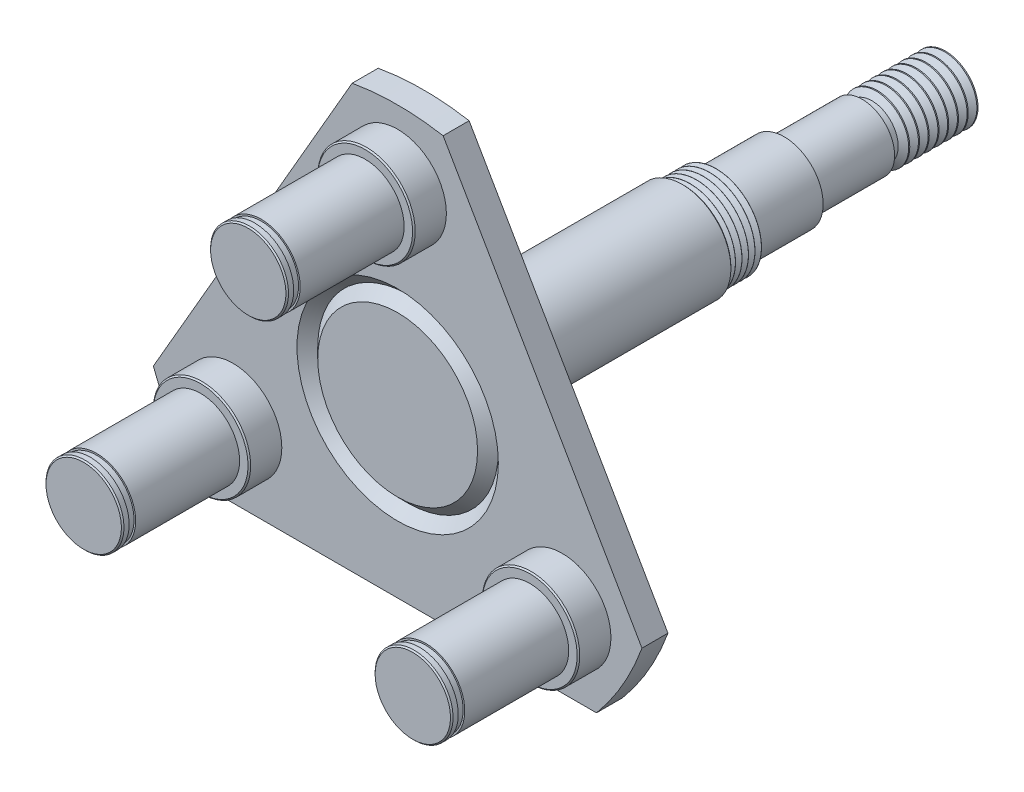
SolidWorks part; units mm, degrees
material "Alloy Steel"
ref_plane "Front Plane" through (0, 0, 0) normal (0, 0, 1) x (1, 0, 0)
ref_plane "Top Plane" through (0, 0, 0) normal (0, 1, 0) x (1, 0, 0)
ref_plane "Right Plane" through (0, 0, 0) normal (1, 0, 0) x (0, 0, -1)
sketch "Sketch2" plane through (0, 0, 0) normal (1, 0, 0) x (0, 0, -1)
  line L0 (88.9771, 0) -> (-33.667, 0) construction
  line L1 (81, 0) -> (-4, 0)
  line L2 (0, 12.5) -> (0, 14)
  line L3 (0, 14) -> (4, 14)
  line L4 (4, 14) -> (4, 10)
  line L5 (4, 10) -> (6, 10)
  line L6 (6, 10) -> (6, 7.5)
  line L7 (6, 7.5) -> (40, 7.5)
  line L8 (45.5, 7) -> (45.5, 6)
  line L9 (0, 12.5) -> (-4, 12.5)
  line L10 (-4, 12.5) -> (-4, 0)
  line L11 (45.5, 6) -> (55.5, 6)
  line L12 (81, 5) -> (81, 0)
  line L13 (40, 7.5) -> (40, 6.25)
  line L14 (40.5, 7) -> (45.5, 7)
  line L15 (40.5, 7) -> (40.5, 6.25)
  line L16 (40.5, 6.25) -> (40, 6.25)
  line L17 (55.5, 6) -> (55.5, 5)
  line L18 (55.5, 5) -> (67.5, 5)
  line L19 (69, 5) -> (69, 4.05)
  line L20 (69, 4.05) -> (67.5, 4.05)
  line L21 (67.5, 4.05) -> (67.5, 5)
  line L22 (69, 5) -> (81, 5)
  dimension "D1" = 28
  dimension "D2" = 20
  dimension "D3" = 15
  dimension "D4" = 4
  dimension "D5" = 2
  dimension "D6" = 39.5
  dimension "D7" = 25
  dimension "D8" = 4
  dimension "D9" = 25.5
  dimension "D10" = 12
  dimension "D11" = 14
  dimension "D12" = 34
  dimension "D13" = 12.5
  dimension "D14" = 0.5
  dimension "D15" = 13.5
  dimension "D16" = 10
  dimension "D17" = 10
  dimension "D18" = 1.5
  dimension "D19" = 8.1
revolve "Revolve1" add sketch "Sketch2" angle 360 about L0
chamfer "Chamfer1" distance 0.2 angle 45 5 edges at (-12.5, 0, 4) (-10, 0, -6) (-14, 0, -4) (-14, 0, 0) (-7.5, 0, -40)
sketch "Sketch3" plane through (0, 0, 0) normal (0, 0, 1) x (1, 0, 0)
  line L0 (-7, 39.3827) -> (-37.6065, -13.6292)
  line L1 (0, 43.7691) -> (0, -26.3413) construction
  line L2 (37.6065, -13.6292) -> (7, 39.3827)
  line L3 (-30.6065, -25.7535) -> (30.6065, -25.7535)
  line L4 (0, 0) -> (0, 29.25) construction
  line L5 (0, 0) -> (25.3312, -14.625) construction
  arc A0 (7, 39.3827) -> (-7, 39.3827) centre (0, 0) ccw
  circle A1 centre (0, 29.25) radius 5
  circle A2 centre (25.3312, -14.625) radius 5
  circle A3 centre (-25.3312, -14.625) radius 5
  arc A4 (-37.6065, -13.6292) -> (-30.6065, -25.7535) centre (0, 0) ccw
  arc A5 (30.6065, -25.7535) -> (37.6065, -13.6292) centre (0, 0) ccw
  circle A6 centre (0, 0) radius 12.5 construction
  circle A7 centre (0, 0) radius 12.5
  dimension "D1" = 29.25
  dimension "D4" = 80
  dimension "D5" = 10
  dimension "D2" = 30
  dimension "D3" = 14
  dimension "D7" = 120
  dimension "D6" = 3
extrude "Boss-Extrude1" add sketch "Sketch3" along normal blind 4
chamfer "Chamfer2" distance 3 angle 45 4 edges at (12.5, 0, 4) (30.3312, -14.625, 0) (-20.3312, -14.625, 0) (5, 29.25, 0)
sketch "Sketch4" plane through (0, 0, 0) normal (1, 0, 0) x (0, 0, -1)
  line L0 (-37.4961, 29.25) -> (6.1179, 29.25) construction
  line L1 (0, 29.25) -> (-3, 29.25) construction
  line L2 (0, 34.25) -> (-4, 34.25)
  line L3 (0, -13.6292) -> (0, 39.3827) construction
  line L4 (-4, -13.6292) -> (-4, 39.3827) construction
  line L5 (-4, 34.25) -> (-4, 36.75)
  line L6 (-4, 36.75) -> (-9, 36.75)
  line L7 (-9, 36.75) -> (-9, 35.25)
  line L8 (-9, 35.25) -> (-27, 35.25)
  line L9 (-27, 35.25) -> (-27, 29.25)
  line L10 (-27, 29.25) -> (0, 29.25)
  line L11 (0, 29.25) -> (0, 34.25)
  dimension "D1" = 10
  dimension "D2" = 15
  dimension "D3" = 12
  dimension "D4" = 5
  dimension "D5" = 18
revolve "Revolve2" add sketch "Sketch4" angle 360 about L0
sketch "Sketch5" plane through (0, 0, 0) normal (1, 0, 0) x (0, 0, -1)
  line L0 (-9, 29.25) -> (-30.4255, 29.25) construction
  line L1 (-9, 35.25) -> (-9, 23.25) construction
  line L2 (-9, 35.25) -> (-27, 35.25) construction
  line L3 (-25, 35.25) -> (-26, 35.25)
  line L4 (-25, 35.25) -> (-25, 35)
  line L5 (-25, 35) -> (-26, 35)
  line L6 (-26, 35.25) -> (-26, 35)
  dimension "D1" = 16
  dimension "D2" = 1
  dimension "D3" = 11.5
revolve "Cut-Revolve1" cut sketch "Sketch5" angle 360 about L0
chamfer "Chamfer3" distance 0.2 angle 45 2 edges at (7.5, 29.25, 9) (6, 29.25, 27)
chamfer "Chamfer4" distance 1 angle 45 1 edges at (5, 29.25, 0)
pattern_circular "CirPattern1" count 3 over 360 about axis through (0, 0, -88.9771) along (0, 0, -1) of "Revolve2", "Cut-Revolve1", "Chamfer3", "Chamfer4"
sketch "Sketch7" plane through (0, 0, 0) normal (1, 0, 0) x (0, 0, -1)
  line L0 (63.4281, 0) -> (30.6953, 0) construction
  line L1 (40, 7.0141) -> (40.5, 6.3)
  line L2 (40.5, 6.3) -> (41, 7.0141)
  line L3 (41, 7.0141) -> (40, 7.0141)
  line L4 (40.5, 7) -> (40.5, -7) construction
  line L5 (40.5, 6.25) -> (40.5, -6.25) construction
  dimension "D1" = 70
  dimension "D2" = 1
  dimension "D3" = 12.6
revolve "Cut-Revolve2" cut sketch "Sketch7" angle 360 about L0
pattern_linear "LPattern1" count 7 spacing 1 along (0, 0, -1) of "Cut-Revolve2"
sketch "Sketch9" plane through (0, 0, 0) normal (1, 0, 0) x (0, 0, -1)
  line L0 (84.685, 0) -> (60.6508, 0) construction
  line L1 (81, 4.05) -> (81.75, 5.1211)
  line L2 (81, -5) -> (81, 5) construction
  line L3 (81.75, 5.1211) -> (80.25, 5.1211)
  line L4 (80.25, 5.1211) -> (81, 4.05)
  dimension "D1" = 70
  dimension "D2" = 1.5
  dimension "D3" = 8.1
revolve "Cut-Revolve3" cut sketch "Sketch9" angle 360 about L0
pattern_linear "LPattern2" count 9 spacing 1.5 along (0, 0, 1) of "Cut-Revolve3"
